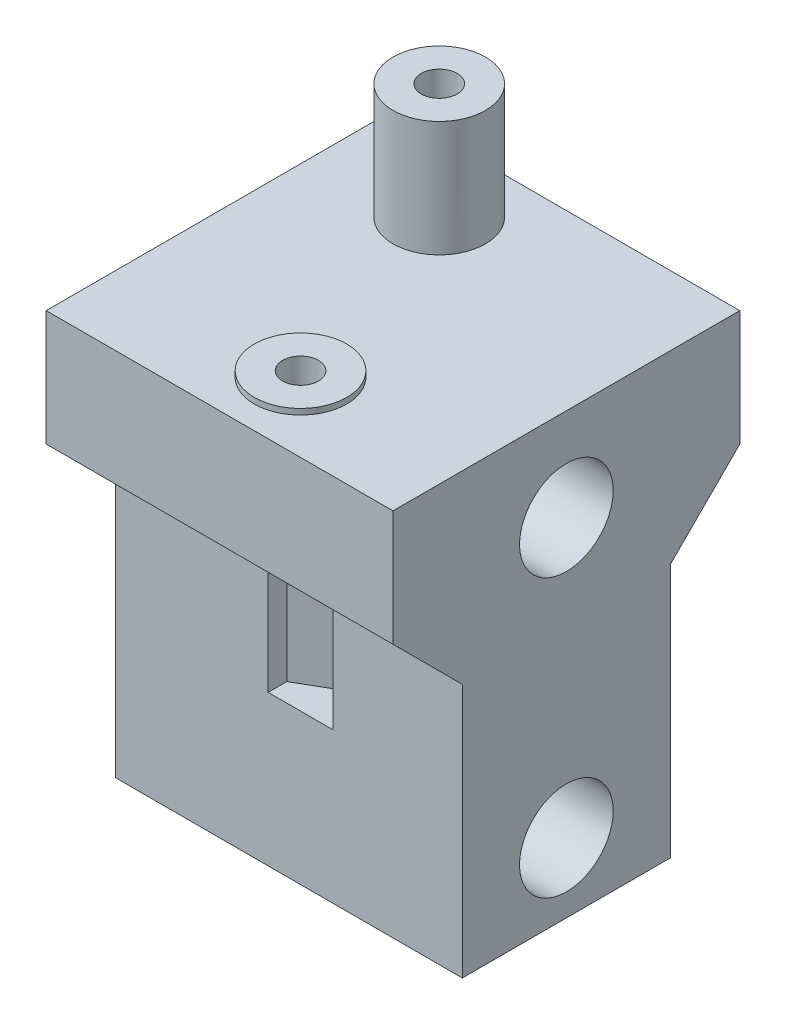
SolidWorks part; units mm, degrees
ref_plane "前视基准面" through (0, 0, 0) normal (0, 0, 1) x (1, 0, 0)
ref_plane "上视基准面" through (0, 0, 0) normal (0, 1, 0) x (1, 0, 0)
ref_plane "右视基准面" through (0, 0, 0) normal (1, 0, 0) x (0, 0, -1)
sketch "草图1" plane through (0, 0, 0) normal (0, 1, 0) x (1, 0, 0)
  line L0 (0, 0) -> (30, 0)
  line L1 (30, 0) -> (30, 30)
  line L2 (30, 30) -> (0, 30)
  line L3 (0, 30) -> (0, 0)
  dimension "D1" = 30
  dimension "D2" = 30
extrude "凸台-拉伸1" add sketch "草图1" along normal blind 38
sketch "草图3" plane through (0, 38, -50) normal (0, -1, 0) x (1, 0, 0)
  line L3 (30, 20) -> (0, 20) construction
  line L4 (30, 50) -> (30, 20) construction
  circle A0 centre (10, 26) radius 4
  dimension "D1" = 8
  dimension "D2" = 6
  dimension "D3" = 20
extrude "凸台-拉伸3" add sketch "草图3" against normal blind 10
sketch "草图7" plane through (0, 38, 0) normal (0, -1, 0) x (1, 0, 0)
  line L1 (30, 0) -> (30, -30) construction
  line L2 (0, 0) -> (30, 0) construction
  circle A0 centre (16, -6) radius 4
  dimension "D1" = 8
  dimension "D2" = 14
  dimension "D3" = 6
extrude "凸台-拉伸4" add sketch "草图7" against normal blind 0.5
ref_plane "基准面1" through (0, 28, 0) normal (0, 1, 0) x (1, 0, 0)
sketch "草图6" plane through (30, 0, 0) normal (1, 0, 0) x (0, 0, -1)
  line L0 (0, 38) -> (0, 0) construction
  line L1 (0, 0) -> (30, 0) construction
  circle A0 centre (15, 6) radius 4.05
  circle A1 centre (15, 30) radius 4.05
  dimension "D4" = 8.1
  dimension "D5" = 8.1
  dimension "D1" = 24
  dimension "D2" = 15
  dimension "D3" = 15
  dimension "D6" = 6
extrude "切除-拉伸3" cut sketch "草图6" against normal through all
sketch "草图9" plane through (0, 28, 0) normal (0, 1, 0) x (1, 0, 0)
  circle A0 centre (16, 6) radius 1.55
  circle A1 centre (10, 24) radius 1.55
  circle A2 centre (10, 24) radius 4 construction
  circle A3 centre (16, 6) radius 4 construction
  dimension "D1" = 3.1
  dimension "D2" = 3.1
extrude "切除-拉伸4" cut sketch "草图9" along normal through all
sketch "草图11" plane through (30, 0, 0) normal (1, 0, 0) x (0, 0, -1)
  line L0 (6, 0) -> (6, 22)
  line L1 (0, 0) -> (30, 0) construction
  line L2 (24, 0) -> (24, 22)
  line L3 (24, 22) -> (30, 28)
  line L4 (16.5, 28) -> (-16.5, 28) construction
  line L5 (30, 38) -> (30, 0) construction
  line L6 (30, 28) -> (30, 0)
  line L7 (30, 0) -> (24, 0)
  line L8 (6, 0) -> (0, 0)
  line L9 (0, 0) -> (0, 28)
  line L10 (0, 38) -> (0, 0) construction
  line L11 (0, 28) -> (6, 22)
  dimension "D1" = 45
  dimension "D2" = 45
  dimension "D3" = 6
  dimension "D4" = 6
extrude "切除-拉伸6" cut sketch "草图11" against normal through all
sketch "草图10" plane through (0, 28, 0) normal (0, 1, 0) x (1, 0, 0)
  line L0 (0, 0) -> (30, 0) construction
  line L1 (18.8, 0) -> (18.8, 7.6166)
  line L2 (18.8, 7.6166) -> (16, 9.2332)
  line L3 (16, 9.2332) -> (13.2, 7.6166)
  line L4 (13.2, 7.6166) -> (13.2, 0)
  line L7 (10, 20.7668) -> (12.8, 22.3834)
  line L8 (12.8, 22.3834) -> (12.8, 30)
  line L11 (7.2, 30) -> (7.2, 22.3834)
  line L12 (7.2, 22.3834) -> (10, 20.7668)
  line L14 (30, 0) -> (30, 30) construction
  line L15 (30, 30) -> (0, 30) construction
  line L16 (0, 30) -> (0, 0) construction
  line L17 (13.2, 4.3834) -> (16, 2.7668) [skipped]
  line L18 (16, 2.7668) -> (18.8, 4.3834) [skipped]
  line L19 (12.8, 25.6166) -> (10, 27.2332) [skipped]
  line L20 (10, 27.2332) -> (7.2, 25.6166) [skipped]
  line L21 (7.2, 30) -> (12.8, 30)
  line L22 (13.2, 0) -> (18.8, 0)
  circle A0 centre (16, 6) radius 2.8 construction
  circle A1 centre (10, 24) radius 2.8 construction
  circle A2 centre (10, 24) radius 1.55 construction
  circle A3 centre (16, 6) radius 1.55 construction
  dimension "D5" = 5.6
  dimension "D6" = 5.6
extrude "切除-拉伸5" cut sketch "草图10" against normal blind 15
sketch "草图12" plane through (0, 0, 0) normal (-1, 0, 0) x (0, 0, 1)
  line L0 (-24, 15) -> (-19.1, 15)
  line L1 (-24, 22) -> (-24, 0) construction
  line L9 (-19.1, 15) -> (-19.1, 0)
  line L10 (0, 28) -> (0, 38)
  line L11 (0, 38) -> (-30, 38)
  line L12 (-30, 38) -> (-30, 28)
  line L15 (-24, 0) -> (-6, 0)
  line L23 (-24, 0) -> (-19.1, 0)
  line L25 (-6, 0) -> (-6, 22)
  line L27 (-6, 22) -> (0, 28)
  line L28 (-30, 28) -> (-24, 22)
  line L29 (-24, 22) -> (-24, 0)
  line L30 (-24, 15) -> (-24, 0)
  dimension "D2" = 15
  dimension "D3" = 4.9
  dimension "D1" = 0
extrude "凸台-拉伸5" add sketch "草图12" along normal blind 7
sketch "草图14" plane through (-7, 0, 0) normal (-1, 0, 0) x (0, 0, 1)
  line L0 (-23.7, 15) -> (-23.7, 2)
  line L1 (-23.7, 2) -> (-24, 2)
  line L4 (-24, 0) -> (-19.1, 0)
  line L5 (-19.1, 0) -> (-19.1, 15)
  line L6 (-19.1, 15) -> (-24, 15)
  line L7 (-24, 15) -> (-24, 0)
  line L10 (-23.7, 15) -> (-24, 15)
  line L11 (-24, 15) -> (-24, 2)
  dimension "D2" = 0.3
  dimension "D3" = 13
  dimension "D1" = 0
extrude "切除-拉伸7" cut sketch "草图14" against normal blind 5
sketch "草图15" plane through (0, 0, -23.7) normal (0, 0, -1) x (-1, 0, 0)
  line L0 (2, 15) -> (7, 15) construction
  line L1 (7, 2) -> (7, 15) construction
  circle A0 centre (4, 12) radius 1
  circle A1 centre (4, 5.5) radius 1
  dimension "D1" = 2
  dimension "D2" = 2
  dimension "D3" = 3
  dimension "D4" = 6.5
  dimension "D5" = 3
  dimension "D6" = 3
extrude "切除-拉伸8" cut sketch "草图15" against normal through all
sketch "草图17" plane through (0, 0, -19.1) normal (0, 0, 1) x (1, 0, 0)
  line L1 (-1.95, 10.8164) -> (-1.95, 13.1836)
  line L2 (-1.95, 13.1836) -> (-4, 14.3671)
  line L3 (-4, 14.3671) -> (-6.05, 13.1836)
  line L4 (-6.05, 13.1836) -> (-6.05, 10.8164)
  line L5 (-6.05, 10.8164) -> (-4, 9.6329)
  line L6 (-4, 9.6329) -> (-1.95, 10.8164)
  line L7 (-7, 0) -> (-7, 15) construction
  line L8 (-1.95, 4.3164) -> (-1.95, 6.6836)
  line L9 (-1.95, 6.6836) -> (-4, 7.8671)
  line L10 (-4, 7.8671) -> (-6.05, 6.6836)
  line L11 (-6.05, 6.6836) -> (-6.05, 4.3164)
  line L12 (-6.05, 4.3164) -> (-4, 3.1329)
  line L13 (-4, 3.1329) -> (-1.95, 4.3164)
  circle A0 centre (-4, 12) radius 2.05 construction
  circle A1 centre (-4, 5.5) radius 2.05 construction
  dimension "D1" = 4.1
  dimension "D2" = 4.1
extrude "切除-拉伸10" cut sketch "草图17" against normal blind 1.8
